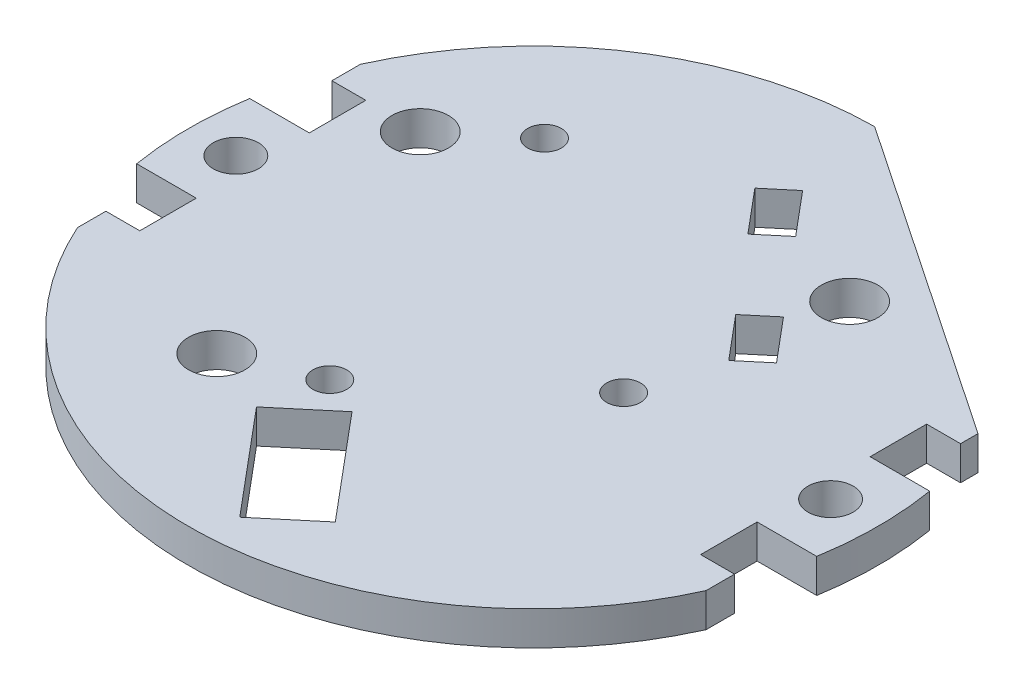
SolidWorks part; units mm, degrees
ref_plane "Alzado" through (0, 0, 0) normal (0, 0, 1) x (1, 0, 0)
ref_plane "Planta" through (0, 0, 0) normal (0, 1, 0) x (1, 0, 0)
ref_plane "Vista lateral" through (0, 0, 0) normal (1, 0, 0) x (0, 0, -1)
sketch "Croquis1" plane through (0, 0, 0) normal (0, 1, 0) x (1, 0, 0)
  circle A0 centre (0, 0) radius 30.5
extrude "Saliente-Extruir1" add sketch "Croquis1" along normal blind 3
sketch "Croquis5" plane through (0, 3, 0) normal (0, 1, 0) x (1, 0, 0)
  line L0 (0, 0) -> (0, 10)
  line L1 (28.8141, -5) -> (30.0874, -5)
  line L2 (28.8141, 5) -> (30.0874, 5)
  line L3 (-24.8141, 10) -> (-28.8141, 10)
  line L4 (24.8141, -5) -> (24.8141, -10)
  line L5 (-24.8141, -10) -> (-28.8141, -10)
  line L6 (24.8141, -5) -> (28.8141, -5)
  line L7 (24.8141, 5) -> (24.8141, 10)
  line L8 (-24.8141, 5) -> (-28.8141, 5)
  line L9 (-24.8141, 5) -> (-24.8141, 10)
  line L10 (-24.8141, -5) -> (-28.8141, -5)
  line L11 (-24.8141, -5) -> (-24.8141, -10)
  line L12 (24.8141, 5) -> (28.8141, 5)
  line L13 (24.8141, -10) -> (28.8141, -10)
  line L14 (24.8141, 10) -> (28.8141, 10)
  line L15 (-28.8141, 5) -> (-30.0874, 5)
  line L16 (-28.8141, -5) -> (-30.0874, -5)
  circle A1 centre (0, 0) radius 30.5 construction
  arc A2 (-28.8141, 10) -> (-30.0874, 5) centre (0, 0) ccw
  arc A3 (28.8141, 10) -> (28.8141, -10) centre (0, 0) cw
  arc A4 (-30.0874, -5) -> (-28.8141, -10) centre (0, 0) ccw
  arc A5 (30.0874, -5) -> (28.8141, -10) centre (0, 0) cw
  arc A6 (28.8141, 10) -> (30.0874, 5) centre (0, 0) cw
  circle M2 centre (0, 0) radius 30.5
extrude "Cortar-Extruir3" cut sketch "Croquis5" against normal blind 4 contours L11 L10 L8 L9 L3 L5 M2 | L15 L8 L9 L3 M2 | L14 L7 L12 L2 M2 | L4 L13 L1 L6 M2 region at (27.1844, 3, 7.3876) region at (27.1844, 3, -7.3876) region at (-27.1844, 3, 7.3876) region at (-27.1844, 3, -7.3876)
sketch "Croquis7" plane through (0, 3, 0) normal (0, 1, 0) x (1, 0, 0)
  line L0 (-8.1011, 29.1011) -> (9.5756, 8.0348)
  line L1 (9.5756, 8.0348) -> (27.2522, -13.0314)
  line L2 (-8.1011, 29.1011) -> (-27.2522, 13.0314)
  line L3 (27.2522, -13.0314) -> (8.1011, -29.1011)
  line L4 (8.1011, -29.1011) -> (-27.2522, 13.0314)
  line L5 (1.4284, 22.4114) -> (-0.8697, 20.4831)
  line L6 (1.4284, 22.4114) -> (4.6423, 18.5812)
  line L7 (4.6423, 18.5812) -> (2.3442, 16.6528)
  line L8 (2.3442, 16.6528) -> (-0.8697, 20.4831)
  line L9 (7.9686, 9.95) -> (11.1825, 6.1197)
  line L10 (8.1011, -29.1011) -> (5.53, -26.0369)
  line L11 (10.2667, 11.8783) -> (13.4807, 8.0481)
  line L12 (13.4807, 8.0481) -> (11.1825, 6.1197)
  line L13 (10.2667, 11.8783) -> (7.9686, 9.95)
  line L14 (5.53, -26.0369) -> (10.8923, -21.5374)
  line L15 (10.8923, -21.5374) -> (-19.3188, 14.4667)
  line L17 (-24.6811, 9.9672) -> (-19.3188, 14.4667)
  point P7 (-9.5756, -8.0348)
extrude "Cortar-Extruir5" cut sketch "Croquis7" against normal blind 4 contours L7 L6 L5 L0 | L11 L13 L0 L1 L12 region at (1.8863, 3, -19.5321) region at (10.7246, 3, -8.999)
sketch "Croquis8" plane through (0, 3, 0) normal (0, 1, 0) x (1, 0, 0)
  line L0 (-11.3137, 11.3137) -> (0, 0)
  line L2 (0, 0) -> (12, 0)
  line L3 (0, 0) -> (-11.3137, 11.3137)
  line L4 (12, 0) -> (12, 16)
  line L5 (0, 0) -> (-12, 0)
  line L6 (-12, 0) -> (-12, -16)
  line L10 (1.5586, -27.5246) -> (6.1549, -23.6679)
  line L11 (6.1549, -23.6679) -> (-1.5586, -14.4754)
  line L13 (-6.1549, -18.3321) -> (-1.5586, -14.4754)
  line L14 (1.5586, -27.5246) -> (-6.1549, -18.3321)
  circle A0 centre (0, 0) radius 30
  circle A1 centre (9, -1) radius 1.5
  circle A2 centre (-5, -13) radius 1.5
  circle A3 centre (-12, -16) radius 2.5
  circle A4 centre (-14, 15) radius 1.5
  circle A5 centre (12, 16) radius 2.5
  point P20 (-3.8567, -16.4037)
extrude "Cortar-Extruir6" cut sketch "Croquis8" against normal blind 10 contours L13 L10 L11 | A3 | L6 A3 | A3 L6 | A5 | L4 A5 | A5 L4 | L14 L10 L11 | L14 L11 | L13 L11 | A4 | L2 A1 | L2 A1 | A2 region at (10.2822, 3, -17.7178) region at (9, 3, -0.2032) region at (9, 3, 1.148) region at (-10.2822, 3, 14.2822) region at (0, 3, 21) region at (-5, 3, 13) region at (-14, 3, -15)
sketch "Croquis10" plane through (0, 3, 0) normal (0, 1, 0) x (1, 0, 0)
  line L0 (-24.8141, 10) -> (-27.8141, 10)
  line L2 (-24.8141, 10) -> (-28.8141, 10) construction
  line L4 (-27.8141, 10) -> (-27.8141, 12.5151)
  line L6 (-27.8141, 10) -> (-28.8141, 10)
  line L14 (-27.8141, -10) -> (-28.8141, -10)
  line L15 (-27.8141, -10) -> (-27.8141, -12.5151)
  line L16 (27.8141, -10) -> (27.8141, -12.5151)
  line L17 (27.8141, -10) -> (28.8141, -10)
  line L21 (27.8141, 10) -> (28.8141, 10)
  line L22 (27.8141, 10) -> (27.8141, 12.5151)
  line L23 (24.8141, 10) -> (27.8141, 10)
  circle A0 centre (-26.3141, 0) radius 2
  circle A1 centre (26.3141, 0) radius 2
  arc A2 (28.8141, 10) -> (-28.8141, 10) centre (0, 0) ccw construction
  arc A5 (-27.8141, 12.5151) -> (-28.8141, 10) centre (0, 0) ccw
  arc A7 (-27.8141, -12.5151) -> (-28.8141, -10) centre (0, 0) cw
  arc A8 (27.8141, -12.5151) -> (28.8141, -10) centre (0, 0) ccw
  arc A10 (27.8141, 12.5151) -> (28.8141, 10) centre (0, 0) cw
  line M13 (24.8141, 10) -> (28.8141, 10)
  arc M14 (28.8141, 10) -> (-28.8141, 10) centre (0, 0) ccw
  line M15 (-28.8141, 10) -> (-24.8141, 10)
  line M21 (-24.8141, -10) -> (-28.8141, -10)
  arc M22 (-28.8141, -10) -> (28.8141, -10) centre (0, 0) ccw
  line M23 (28.8141, -10) -> (24.8141, -10)
extrude "Cortar-Extruir8" cut sketch "Croquis10" against normal blind 3 contours L15 M21 M22 | L4 M15 M14 | L16 M23 M22 | L22 M13 M14 | A0 | A1 | L22 A10 L21 region at (-28.1547, 3, -10.8559) region at (28.1547, 3, -10.8559) region at (-28.1547, 3, 10.8559) region at (28.1547, 3, 10.8559) region at (-26.3141, 3, 0) region at (26.3141, 3, 0)
sketch "Croquis11" plane through (0, 3, 0) normal (0, 1, 0) x (1, 0, 0)
  line L0 (0, 0) -> (-20, 0)
  line L1 (-20, 0) -> (-20, 10)
  line L2 (0, 0) -> (0, 4.5949)
  line L3 (29.8013, 10.2046) -> (-1.7022, 31.454)
  circle A0 centre (-20, 10) radius 2.5
  circle A5 centre (0, 0) radius 31.5
  line M20 (27.8141, 10) -> (27.8141, 12.5151)
  arc M21 (27.8141, 12.5151) -> (-27.8141, 12.5151) centre (0, 0) ccw
extrude "Cortar-Extruir9" cut sketch "Croquis11" against normal blind 3 contours L3 M20 M21 | A0 region at (15.2326, 3, -22.6507) region at (-18.2822, 3, -8.2822)
